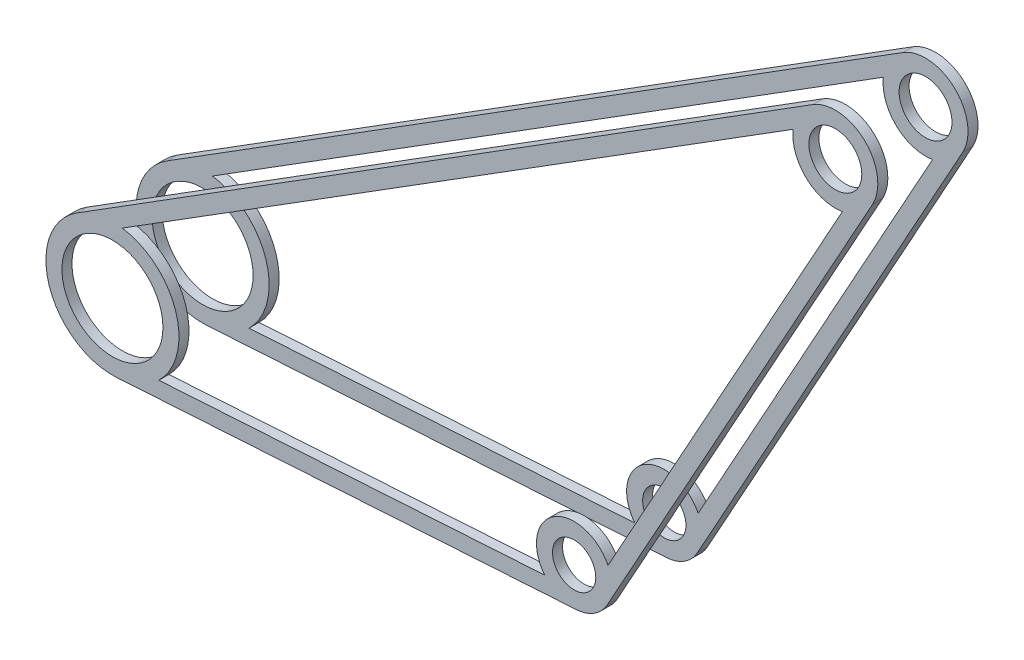
SolidWorks part; units mm, degrees
ref_plane "Front Plane" through (0, 0, 0) normal (0, 0, 1) x (1, 0, 0)
ref_plane "Top Plane" through (0, 0, 0) normal (0, 1, 0) x (1, 0, 0)
ref_plane "Right Plane" through (0, 0, 0) normal (1, 0, 0) x (0, 0, -1)
sketch "Sketch1" plane through (0, 0, 0) normal (0, 0, 1) x (1, 0, 0)
  line L0 (0, 0) -> (73.152, 0) construction
  line L1 (73.152, 0) -> (114.5399, 76.3747) construction
  line L2 (114.5399, 76.3747) -> (0, 0) construction
  line L3 (-5.6029, 8.9286) -> (110.9621, 82.0761)
  line L4 (120.4295, 73.1159) -> (78.3748, -2.8898)
  line L5 (73.5251, -5.9573) -> (0.6588, -10.5204)
  line L6 (-4.2528, 6.7771) -> (112.3122, 79.9246)
  line L7 (0.5001, -7.9854) -> (73.3663, -3.4223)
  line L8 (76.1523, -1.6601) -> (118.207, 74.3457)
  circle A0 centre (0, 0) radius 8.001
  circle A1 centre (73.152, 0) radius 3.429
  circle A2 centre (114.5399, 76.3747) radius 4.191
  circle A3 centre (0, 0) radius 10.541
  circle A4 centre (73.152, 0) radius 5.969
  circle A5 centre (114.5399, 76.3747) radius 6.731
  dimension "D1" = 8.382
  dimension "D2" = 6.858
  dimension "D3" = 16.002
  dimension "D6" = 2.54
  dimension "D7" = 2.54
  dimension "D8" = 2.54
  dimension "D4" = 73.152
  dimension "D5" = 86.868
  dimension "D9" = 137.668
extrude "Boss-Extrude1" add sketch "Sketch1" along normal blind 1.5875 from offset 6.35 contours A5 L3 A3 L6 | L6 A3 A0 | A4 A3 L5 | A4 L8 A1 | A5 L8 A4 L4 | A5 L6 A2 L8 | A3 L6 A0 | L8 A4 A1 | L6 A5 L8 A2 region at (-2.0989, 10.0476, 0) region at (53.7785, 44.7109, 0) region at (117.7058, 82.0991, 0) region at (37.6389, -6.9621, 0) region at (7.8072, 6.7258, 0) region at (111.5933, 73.2613, 0) region at (75.1084, -3.0932, 0) region at (98.251, 35.6128, 0) region at (70.041, 4.9185, 0)
extrude "Boss-Extrude2" add sketch "Sketch1<4>" against normal blind 1.5875 from offset 6.35 separate body contours A5 L3 A3 L6 | L6 A3 A0 | A3 L6 A0 | A4 A3 L5 | A4 L8 A1 | L8 A4 A1 | A5 L8 A4 L4 | L6 A5 L8 A2 | A5 L6 A2 L8 region at (-2.0989, 10.0476, 0) region at (53.7785, 44.7109, 0) region at (117.7058, 82.0991, 0) region at (37.6389, -6.9621, 0) region at (7.8072, 6.7258, 0) region at (111.5933, 73.2613, 0) region at (75.1084, -3.0932, 0) region at (98.251, 35.6128, 0) region at (70.041, 4.9185, 0) offset against normal yes
sketch "Sketch1<4>" plane through (0, 0, 0) normal (0, 0, 1) x (1, 0, 0) same geometry as "Sketch1"
equation "\"D19@Boss-Extrude2\"=.45"
